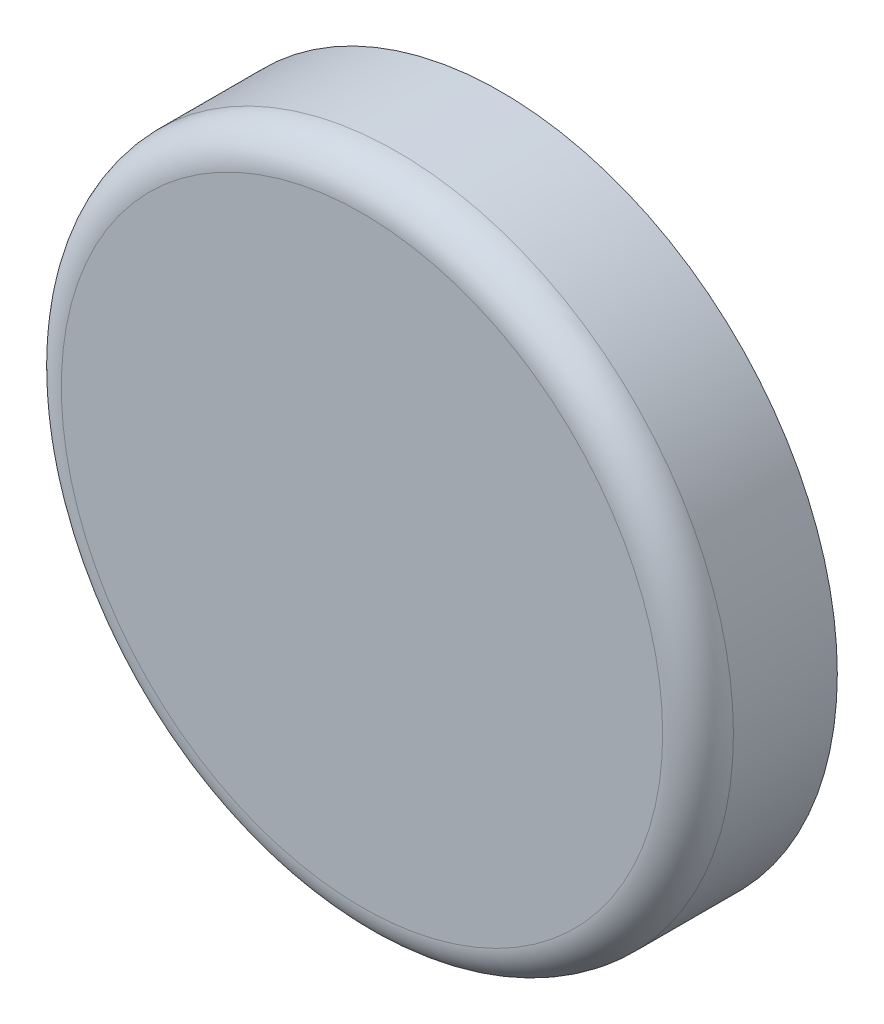
SolidWorks part; units mm, degrees
ref_plane "Front Plane" through (0, 0, 0) normal (0, 0, 1) x (1, 0, 0)
ref_plane "Top Plane" through (0, 0, 0) normal (0, 1, 0) x (1, 0, 0)
ref_plane "Right Plane" through (0, 0, 0) normal (1, 0, 0) x (0, 0, -1)
sketch "Sketch1" plane through (0, 0, 0) normal (0, 0, 1) x (1, 0, 0)
  circle A0 centre (0, 0) radius 12.065
  dimension "D1" = 24.13
extrude "Boss-Extrude1" add sketch "Sketch1" along normal blind 5
fillet "Fillet1" radius 1.27 1 edges at (12.065, 0, 5)
sketch "Sketch2" plane through (0, 0, 0) normal (0, 0, -1) x (-1, 0, 0)
  line L0 (0, 12.065) -> (0, -12.065) construction
  line L1 (-2.3, -2.3) -> (2.3, -2.3) construction
  line L2 (-2.3, -2.3) -> (-2.3, 2.3) construction
  line L3 (-2.3, 2.3) -> (2.3, 2.3) construction
  line L4 (2.3, -2.3) -> (2.3, 2.3) construction
  line L5 (-2.3, -2.3) -> (2.3, 2.3) construction
  line L6 (-2.3, 2.3) -> (2.3, -2.3) construction
  line L7 (-12.065, 0) -> (12.065, 0) construction
  line L8 (2.3, 1.284) -> (3.316, 1.284)
  line L9 (-1.284, 2.3) -> (1.284, 2.3)
  line L10 (-1.284, 2.3) -> (-1.284, 3.316)
  line L11 (-1.284, 3.316) -> (1.284, 3.316)
  line L12 (1.284, 2.3) -> (1.284, 3.316)
  line L13 (2.3, 1.284) -> (2.3, -1.284)
  line L14 (2.3, -1.284) -> (3.316, -1.284)
  line L15 (3.316, 1.284) -> (3.316, -1.284)
  line L16 (1.284, -2.3) -> (1.284, -3.316)
  line L17 (1.284, -2.3) -> (-1.284, -2.3)
  line L18 (-1.284, -2.3) -> (-1.284, -3.316)
  line L19 (1.284, -3.316) -> (-1.284, -3.316)
  line L20 (-2.3, -1.284) -> (-3.316, -1.284)
  line L21 (-2.3, -1.284) -> (-2.3, 1.284)
  line L22 (-2.3, 1.284) -> (-3.316, 1.284)
  line L23 (-3.316, -1.284) -> (-3.316, 1.284)
  circle A0 centre (0, 0) radius 12.065 construction
  point P0 (0, 0)
  point P17 (1.2438, -3.7038)
  point P18 (0, 3.316)
  point P19 (0, 0)
  point P33 (0, 0)
  dimension "D1" = 4.6
  dimension "D2" = 4.6
  dimension "D3" = 1.016
  dimension "D4" = 1.016
  dimension "D5" = 4
extrude "Boss-Extrude2" add sketch "Sketch2" along normal blind 1.524
